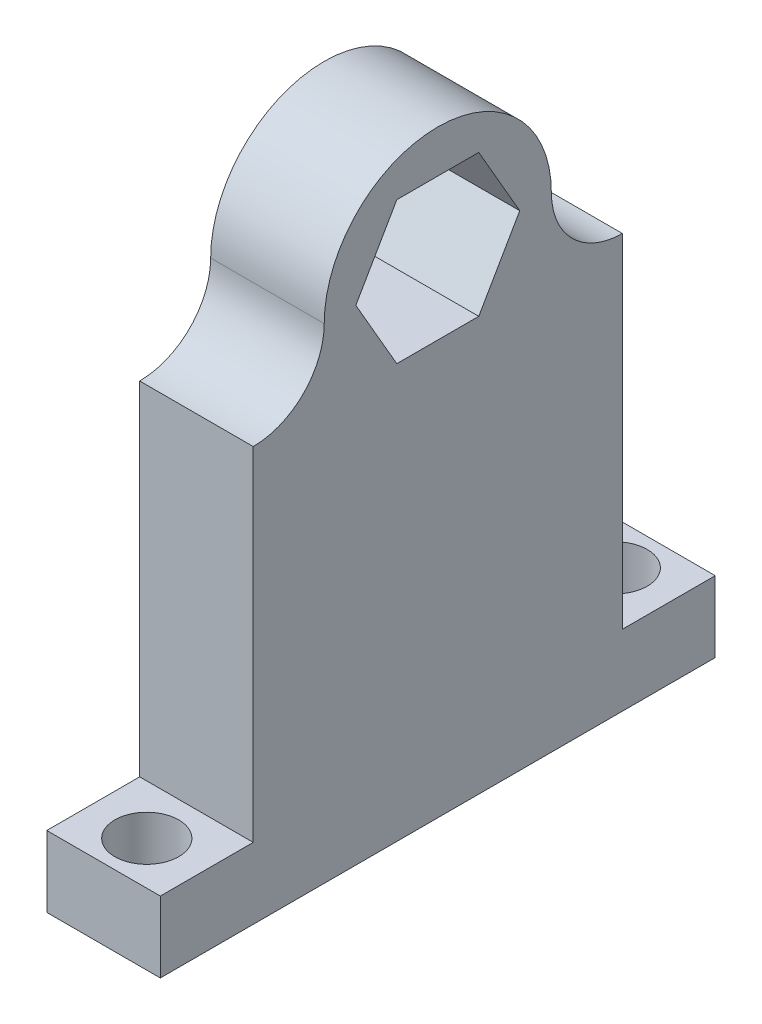
SolidWorks part; units mm, degrees
ref_plane "Спереди" through (0, 0, 0) normal (0, 0, 1) x (1, 0, 0)
ref_plane "Сверху" through (0, 0, 0) normal (0, 1, 0) x (1, 0, 0)
ref_plane "Справа" through (0, 0, 0) normal (1, 0, 0) x (0, 0, -1)
sketch "Эскиз1" plane through (0, 0, 0) normal (1, 0, 0) x (0, 0, -1)
  line L6 (-8, 0) -> (8, 0) construction
  line L12 (-13, -5) -> (-13, -10)
  line L13 (13, -5) -> (13, -10)
  line L15 (-13, -10) -> (13, -10)
  arc A0 (8, 0) -> (-8, 0) centre (0, 0) ccw
  arc A1 (-13, -5) -> (-8, 0) centre (-13, 0) ccw
  arc A2 (8, 0) -> (13, -5) centre (13, 0) ccw
  point P4 (0, 0)
  point P7 (0, -39.795)
  point P9 (0, 8)
  dimension "D1" = 16
  dimension "D4" = 10
  dimension "D5" = 10
  dimension "D2" = 5
extrude "Бобышка-Вытянуть1" add sketch "Эскиз1" along normal blind 8
sketch "Эскиз2" plane through (8, 0, 0) normal (1, 0, 0) x (0, 0, -1)
  line L1 (5.7735, 0) -> (2.8868, 5)
  line L2 (2.8868, 5) -> (-2.8868, 5)
  line L3 (-2.8868, 5) -> (-5.7735, 0)
  line L4 (-5.7735, 0) -> (-2.8868, -5)
  line L5 (-2.8868, -5) -> (2.8868, -5)
  line L6 (2.8868, -5) -> (5.7735, 0)
  circle A0 centre (0, 0) radius 5 construction
  dimension "D1" = 10
extrude "Вырез-Вытянуть1" cut sketch "Эскиз2" against normal through all
sketch "Эскиз4" plane through (0, -10, 0) normal (0, -1, 0) x (1, 0, 0)
  line L8 (0, 13) -> (0, -13)
  line L9 (0, -13) -> (8, -13)
  line L10 (8, -13) -> (8, 13)
  line L11 (8, 13) -> (0, 13)
  line L12 (0, 13) -> (0, -13)
  line L13 (0, -13) -> (8, -13)
  line L14 (8, -13) -> (8, 13)
  line L15 (8, 13) -> (0, 13)
  dimension "D1" = 0
extrude "Бобышка-Вытянуть2" add sketch "Эскиз4" along normal up to surface (24.15 mm away)
sketch "Эскиз5" plane through (0, -34.15, 0) normal (0, -1, 0) x (1, 0, 0)
  line L1 (0, 19.5455) -> (8, 19.5455)
  line L2 (0, 19.5455) -> (0, -19.5455)
  line L3 (0, -19.5455) -> (8, -19.5455)
  line L4 (8, 19.5455) -> (8, -19.5455)
  line L8 (4, -16.5) -> (4, 16.5) construction
  line L9 (8, -19.5455) -> (0, 19.5455) construction
  line L10 (0, -19.5455) -> (8, 19.5455) construction
  circle A0 centre (4, -16.5) radius 2.25
  circle A1 centre (4, 16.5) radius 2.25
  dimension "Диаметр001" = 4.5
  dimension "Диаметр002" = 4.5
  dimension "X001" = 4
  dimension "X002" = 4
  dimension "Y001" = 19.5455
  dimension "Y002" = 3.0455
  dimension "Y003" = 33
  dimension "Y004" = 3.0455
extrude "Бобышка-Вытянуть3" add sketch "Эскиз5" against normal blind 5
ref_axis "Ось_крепления_гайки_33" through (4, -34.15, -16.5) along (0, 1, 0)
ref_axis "Ось_крепления_гайки_34" through (4, -34.15, 16.5) along (0, 1, 0)
